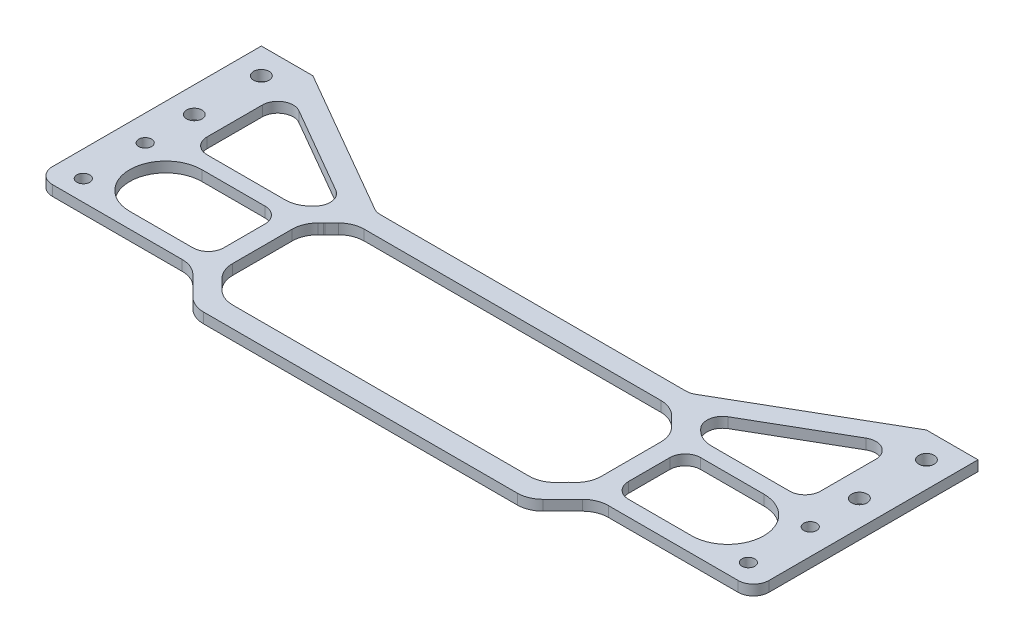
SolidWorks part; units mm, degrees
material "Thornel Mat VMA"
ref_plane "前视基准面" through (0, 0, 0) normal (0, 0, 1) x (1, 0, 0)
ref_plane "上视基准面" through (0, 0, 0) normal (0, 1, 0) x (1, 0, 0)
ref_plane "右视基准面" through (0, 0, 0) normal (1, 0, 0) x (0, 0, -1)
sketch "草图1" plane through (0, 0, 0) normal (0, 1, 0) x (1, 0, 0)
  line L1 (66.5, 10) -> (-66.5, 10)
  line L2 (69.5, 7) -> (69.5, -7)
  line L3 (66.5, -10) -> (-66.5, -10)
  line L4 (-69.5, 7) -> (-69.5, -7)
  line L5 (69.5, 10) -> (-69.5, -10) construction
  line L6 (69.5, -10) -> (-69.5, 10) construction
  arc A0 (69.5, 7) -> (66.5, 10) centre (66.5, 7) ccw
  arc A1 (69.5, -7) -> (66.5, -10) centre (66.5, -7) cw
  arc A2 (-66.5, -10) -> (-69.5, -7) centre (-66.5, -7) cw
  arc A3 (-66.5, 10) -> (-69.5, 7) centre (-66.5, 7) ccw
  point P0 (0, 0)
  dimension "D3" = 3
  dimension "D1" = 20
  dimension "D2" = 139
extrude "凸台-拉伸1" add sketch "草图1" along normal blind 2
sketch "草图2" plane through (0, 2, 0) normal (0, 1, 0) x (1, 0, 0)
  line L1 (64.5, 6) -> (-64.5, 6)
  line L2 (64.5, 6) -> (64.5, -6)
  line L3 (64.5, -6) -> (-64.5, -6)
  line L4 (-64.5, 6) -> (-64.5, -6)
  line L5 (64.5, 6) -> (-64.5, -6) construction
  line L6 (64.5, -6) -> (-64.5, 6) construction
  point P0 (0, 0)
  dimension "D1" = 12
  dimension "D2" = 129
hole_wizard "孔1" positions "草图3" profile "草图4" legacy end condition through all
sketch "草图3" plane through (0, 2, 0) normal (0, 1, 0) x (1, 0, 0)
  point P0 (-64.5, 6)
  point P3 (-64.5, -6)
  point P6 (64.5, -6)
  point P9 (64.5, 6)
sketch "草图4" plane through (-64.5, 2, -6) normal (1, 0, 0) x (0, 0, 1)
  line L0 (0, 0) -> (0, 2)
  line L1 (0, 2) -> (1.25, 2)
  line L2 (1.25, 2) -> (1.25, 0)
  line L3 (1.25, 0) -> (0, 0)
  line L4 (0, 110) -> (0, -10) construction
  dimension "直径" = 2.5
  dimension "深度" = 2
sketch "草图5" plane through (0, 2, 0) normal (0, 1, 0) x (1, 0, 0)
  line L0 (-54.5, 0) -> (54.5, 0) construction
  line L1 (-54.5, 7) -> (54.5, 7)
  line L2 (-54.5, -7) -> (54.5, -7)
  line L3 (66.5, 10) -> (-66.5, 10) construction
  line L4 (-69.5, 7) -> (-69.5, -7) construction
  arc A0 (-54.5, 7) -> (-54.5, -7) centre (-54.5, 0) ccw
  arc A1 (54.5, -7) -> (54.5, 7) centre (54.5, 0) ccw
  point P3 (0, 0)
  dimension "D1" = 3
  dimension "D2" = 15
extrude "切除-拉伸1" cut sketch "草图5" against normal through all
sketch "草图6" plane through (0, 0, 0) normal (0, -1, 0) x (1, 0, 0)
  line L0 (-66.5, 10) -> (66.5, 10) construction
  line L1 (-39.25, -10) -> (39.25, -10)
  line L2 (-39.25, -4) -> (-39.25, 4)
  line L3 (-39.25, 10) -> (39.25, 10)
  line L4 (39.25, -4) -> (39.25, 4)
  line L5 (-39.25, -10) -> (39.25, 10) construction
  line L6 (-39.25, 10) -> (39.25, -10) construction
  line L7 (39.25, -23.75) -> (39.25, 23.75) construction
  line L8 (39.25, 10) -> (46.786, 7)
  line L9 (-54.5, 7) -> (54.5, 7) construction
  line L10 (46.786, 7) -> (42.25, 7)
  line L11 (39.25, -10) -> (46.786, -7)
  line L12 (54.5, -7) -> (-54.5, -7) construction
  line L13 (46.786, -7) -> (42.25, -7)
  line L14 (-39.25, 10) -> (-46.786, 7)
  line L15 (-46.786, 7) -> (-42.25, 7)
  line L16 (-39.25, -10) -> (-46.4944, -7)
  line L17 (-46.4944, -7) -> (-42.25, -7)
  line L18 (-39.25, 23.75) -> (-39.25, -23.75) construction
  arc A0 (39.25, -4) -> (42.25, -7) centre (42.25, -4) ccw
  arc A1 (39.25, 4) -> (42.25, 7) centre (42.25, 4) cw
  arc A2 (-42.25, -7) -> (-39.25, -4) centre (-42.25, -4) ccw
  arc A3 (-39.25, 4) -> (-42.25, 7) centre (-42.25, 4) ccw
  point P0 (0, 0)
  point P26 (39.25, -7)
  point P29 (39.25, 7)
  point P32 (-39.25, -7)
  point P35 (-39.25, 7)
  dimension "D1" = 3
extrude "凸台-拉伸2" add sketch "草图6" against normal blind 2
sketch "草图7" plane through (0, 0, 0) normal (0, -1, 0) x (1, 0, 0)
  line L0 (34.25, 0) -> (-34.25, 0) construction
  line L1 (34.25, -1.5) -> (-34.25, -1.5)
  line L2 (34.25, 1.5) -> (-34.25, 1.5)
  line L3 (39.25, -4) -> (39.25, 4) construction
  line L4 (34.25, 5.5) -> (-34.25, 5.5) construction
  line L5 (34.25, 4) -> (-34.25, 4)
  line L6 (34.25, 7) -> (-34.25, 7)
  line L7 (34.25, -5.5) -> (-34.25, -5.5) construction
  line L8 (34.25, -7) -> (-34.25, -7)
  line L9 (34.25, -4) -> (-34.25, -4)
  arc A0 (34.25, -1.5) -> (34.25, 1.5) centre (34.25, 0) ccw
  arc A1 (-34.25, 1.5) -> (-34.25, -1.5) centre (-34.25, 0) ccw
  arc A2 (34.25, 4) -> (34.25, 7) centre (34.25, 5.5) ccw
  arc A3 (-34.25, 7) -> (-34.25, 4) centre (-34.25, 5.5) ccw
  arc A4 (34.25, -7) -> (34.25, -4) centre (34.25, -5.5) ccw
  arc A5 (-34.25, -4) -> (-34.25, -7) centre (-34.25, -5.5) ccw
  point P3 (0, 0)
  point P14 (0, 5.5)
  point P21 (0, -5.5)
  dimension "D1" = 1.5
  dimension "D2" = 5
  dimension "D4" = 5.5
  dimension "D3" = 2
  dimension "D5" = 2
extrude "切除-拉伸2" cut sketch "草图7" against normal through all both and the other way through all
sketch "草图9" plane through (0, 0, 0) normal (0, -1, 0) x (-1, 0, 0)
  line L0 (47.6578, -10) -> (41.3211, -10)
  line L1 (66.5, -10) -> (-66.5, -10) construction
  line L2 (39.25, -23.75) -> (39.25, 23.75) construction
  line L3 (37.7855, -11.4645) -> (33.9645, -15.2855)
  line L4 (30.4289, -16.75) -> (-30.4289, -16.75)
  line L5 (0, 87.7971) -> (0, -87.7971) construction
  line L6 (39.25, -10) -> (33.5931, -10)
  line L7 (33.5931, -10) -> (32.3076, -11.2855)
  line L8 (28.7721, -12.75) -> (-28.7721, -12.75)
  line L9 (-36.25, -26.75) -> (36.25, -26.75) construction
  line L10 (47.6578, -10) -> (47.6578, -7.8784)
  line L11 (47.6578, -7.8784) -> (24.5865, -7.8784)
  line L12 (24.5865, -7.8784) -> (24.5865, -10)
  line L13 (24.5865, -10) -> (33.5931, -10)
  line L14 (0, -16.75) -> (0, 0) construction
  line L15 (-31.7712, 0) -> (31.7712, 0) construction
  line L16 (24.5865, 10) -> (33.5931, 10)
  line L17 (24.5865, 7.8784) -> (24.5865, 10)
  line L18 (47.6578, 7.8784) -> (24.5865, 7.8784)
  line L19 (47.6578, 10) -> (47.6578, 7.8784)
  line L20 (28.7721, 12.75) -> (-28.7721, 12.75)
  line L21 (33.5931, 10) -> (32.3076, 11.2855)
  line L22 (39.25, 10) -> (33.5931, 10)
  line L23 (30.4289, 16.75) -> (-30.4289, 16.75)
  line L24 (37.7855, 11.4645) -> (33.9645, 15.2855)
  line L25 (47.6578, 10) -> (41.3211, 10)
  line L26 (-47.6578, 10) -> (-41.3211, 10)
  line L27 (-37.7855, 11.4645) -> (-33.9645, 15.2855)
  line L28 (-39.25, 10) -> (-33.5931, 10)
  line L29 (-33.5931, 10) -> (-32.3076, 11.2855)
  line L30 (-47.6578, 10) -> (-47.6578, 7.8784)
  line L31 (-47.6578, 7.8784) -> (-24.5865, 7.8784)
  line L32 (-24.5865, 7.8784) -> (-24.5865, 10)
  line L33 (-24.5865, 10) -> (-33.5931, 10)
  line L34 (-24.5865, -10) -> (-33.5931, -10)
  line L35 (-24.5865, -7.8784) -> (-24.5865, -10)
  line L36 (-47.6578, -7.8784) -> (-24.5865, -7.8784)
  line L37 (-47.6578, -10) -> (-47.6578, -7.8784)
  line L38 (-33.5931, -10) -> (-32.3076, -11.2855)
  line L39 (-39.25, -10) -> (-33.5931, -10)
  line L40 (-37.7855, -11.4645) -> (-33.9645, -15.2855)
  line L41 (-47.6578, -10) -> (-41.3211, -10)
  arc A0 (28.7721, -12.75) -> (32.3076, -11.2855) centre (28.7721, -7.75) ccw
  arc A1 (37.7855, -11.4645) -> (41.3211, -10) centre (41.3211, -15) cw
  arc A2 (30.4289, -16.75) -> (33.9645, -15.2855) centre (30.4289, -11.75) ccw
  arc A3 (30.4289, 16.75) -> (33.9645, 15.2855) centre (30.4289, 11.75) cw
  arc A4 (37.7855, 11.4645) -> (41.3211, 10) centre (41.3211, 15) ccw
  arc A5 (28.7721, 12.75) -> (32.3076, 11.2855) centre (28.7721, 7.75) cw
  arc A6 (-28.7721, 12.75) -> (-32.3076, 11.2855) centre (-28.7721, 7.75) ccw
  arc A7 (-37.7855, 11.4645) -> (-41.3211, 10) centre (-41.3211, 15) cw
  arc A8 (-30.4289, 16.75) -> (-33.9645, 15.2855) centre (-30.4289, 11.75) ccw
  arc A9 (-30.4289, -16.75) -> (-33.9645, -15.2855) centre (-30.4289, -11.75) cw
  arc A10 (-37.7855, -11.4645) -> (-41.3211, -10) centre (-41.3211, -15) ccw
  arc A11 (-28.7721, -12.75) -> (-32.3076, -11.2855) centre (-28.7721, -7.75) cw
  point P65 (0, 16.75)
  point P67 (0, 12.75)
  point P75 (0, -12.75)
  line M31 (66.5, 10) -> (-66.5, 10)
  line M35 (-66.5, -10) -> (66.5, -10)
  dimension "D5" = 5
  dimension "D6" = 5
  dimension "D1" = 4
  dimension "D2" = 45
  dimension "D3" = 4
  dimension "D4" = 10
extrude "凸台-拉伸3" add sketch "草图9" against normal blind 2 contours L8 A11 L38 A10 L40 A9 L4 A2 L3 A1 L7 A0 M35 | L23 A8 L27 A7 L29 A6 L20 A5 L21 A4 L24 A3 M31 region at (0, 0, 14.3452) region at (0, 0, -14.3452)
sketch "草图10" plane through (0, 2, 0) normal (0, 1, 0) x (1, 0, 0)
  line L0 (34.2855, -9.3076) -> (34.098, -9.4951)
  line L2 (-35.75, -5.7721) -> (-35.75, 5.7721)
  line L4 (35.75, -5.7721) -> (35.75, 5.7721)
  line L5 (-35.75, -7.8431) -> (35.75, 7.8431) construction
  line L6 (-35.75, 7.8431) -> (35.75, -7.8431) construction
  line L7 (33.5931, -10) -> (32.3076, -11.2855) construction
  line L8 (30.5884, -10.9595) -> (-30.2214, -11.2747)
  line L9 (-33.7828, -9.8103) -> (-34.2855, -9.3076)
  line L10 (34.2855, 9.3076) -> (33.7721, 9.8211)
  line L11 (30.2365, 11.2855) -> (-30.2365, 11.2855)
  line L12 (-33.7721, 9.8211) -> (-34.2855, 9.3076)
  arc A0 (34.25, 4) -> (34.25, 7) centre (34.25, 5.5) ccw construction
  arc A1 (-35.75, -5.7721) -> (-34.2855, -9.3076) centre (-30.75, -5.7721) ccw
  arc A2 (-33.7828, -9.8103) -> (-30.2214, -11.2747) centre (-30.2473, -6.2748) ccw
  arc A3 (-35.75, 5.7721) -> (-34.2855, 9.3076) centre (-30.75, 5.7721) cw
  arc A4 (-33.7721, 9.8211) -> (-30.2365, 11.2855) centre (-30.2365, 6.2855) cw
  arc A5 (30.2365, 11.2855) -> (33.7721, 9.8211) centre (30.2365, 6.2855) cw
  arc A6 (34.2855, 9.3076) -> (35.75, 5.7721) centre (30.75, 5.7721) cw
  arc A7 (35.75, -5.7721) -> (34.2855, -9.3076) centre (30.75, -5.7721) cw
  arc A8 (30.5884, -10.9595) -> (34.098, -9.4951) centre (30.5625, -5.9596) ccw
  point P0 (0, 0)
  point P23 (-32.3076, -11.2855)
  point P29 (-32.3076, 11.2855)
  point P32 (32.3076, 11.2855)
  point P41 (32.6443, -10.9489)
  dimension "D1" = 5
extrude "切除-拉伸3" cut sketch "草图10" against normal through all both and the other way through all
sketch "草图11" plane through (0, 0, 0) normal (0, -1, 0) x (1, 0, 0)
  line L0 (-69.5, -7) -> (-69.5, -33.5342)
  line L1 (-69.5, -10) -> (-69.5, -220) construction
  line L2 (-69.5, -33.5342) -> (-59.5, -33.5342)
  line L3 (-59.5, -10) -> (-59.5, -220) construction
  line L4 (-30.4289, -16.75) -> (30.4289, -16.75) construction
  line L5 (-59.5, -33.5342) -> (-31.1251, -17.1519)
  line L6 (0, -12.75) -> (0, -36.5409) construction
  line L7 (-38.056, -16.5347) -> (-55, -26.3173)
  line L8 (-59.5, -23.7192) -> (-59.5, -13)
  line L9 (-41.3211, -10) -> (-66.5, -10) construction
  line L10 (-56.5, -10) -> (-53.1843, -10)
  line L11 (-53.1843, -10) -> (-53.1843, -7.988)
  line L12 (-53.1843, -7.988) -> (-66.362, -7.988)
  line L13 (-66.362, -7.988) -> (-69.5, -7)
  line L14 (-39.9409, -9.3091) -> (-37.4347, -11.8153)
  line L15 (-37.7855, -11.4645) -> (-33.9645, -15.2855) construction
  line L16 (-39.9409, -9.3091) -> (-32.2298, -13.6308)
  line L17 (-32.2298, -13.6308) -> (-21.7891, -16.75)
  line L18 (-21.7891, -16.75) -> (-29.6251, -16.75)
  line L19 (-28.7721, -12.75) -> (28.7721, -12.75) construction
  line L20 (0, -87.7971) -> (0, 87.7971) construction
  line L21 (21.7891, -16.75) -> (29.6251, -16.75)
  line L22 (32.2298, -13.6308) -> (21.7891, -16.75)
  line L23 (39.9409, -9.3091) -> (32.2298, -13.6308)
  line L24 (39.9409, -9.3091) -> (37.4347, -11.8153)
  line L25 (66.362, -7.988) -> (69.5, -7)
  line L26 (53.1843, -7.988) -> (66.362, -7.988)
  line L27 (53.1843, -10) -> (53.1843, -7.988)
  line L28 (56.5, -10) -> (53.1843, -10)
  line L29 (59.5, -23.7192) -> (59.5, -13)
  line L30 (38.056, -16.5347) -> (55, -26.3173)
  line L31 (59.5, -33.5342) -> (31.1251, -17.1519)
  line L32 (69.5, -33.5342) -> (59.5, -33.5342)
  line L33 (69.5, -7) -> (69.5, -33.5342)
  arc A0 (-38.056, -16.5347) -> (-37.4347, -11.8153) centre (-39.556, -13.9366) ccw
  arc A1 (-55, -26.3173) -> (-59.5, -23.7192) centre (-56.5, -23.7192) cw
  arc A2 (-59.5, -13) -> (-56.5, -10) centre (-56.5, -13) cw
  arc A3 (-29.6251, -16.75) -> (-31.1251, -17.1519) centre (-29.6251, -19.75) ccw
  arc A4 (29.6251, -16.75) -> (31.1251, -17.1519) centre (29.6251, -19.75) cw
  arc A5 (59.5, -13) -> (56.5, -10) centre (56.5, -13) ccw
  arc A6 (55, -26.3173) -> (59.5, -23.7192) centre (56.5, -23.7192) ccw
  arc A7 (38.056, -16.5347) -> (37.4347, -11.8153) centre (39.556, -13.9366) cw
  point P25 (-30.4289, -16.75)
  point P28 (-34.6701, -14.5799)
  point P31 (-59.5, -28.9154)
  point P34 (-59.5, -10)
  point P64 (59.5, -10)
  point P65 (59.5, -28.9154)
  point P66 (34.6701, -14.5799)
  point P67 (30.4289, -16.75)
  dimension "D1" = 3
  dimension "D3" = 3
  dimension "D2" = 150
  dimension "D4" = 4
extrude "凸台-拉伸4" add sketch "草图11" against normal blind 2
hole_wizard "孔2" positions "草图12" profile "草图13" legacy end condition through all
sketch "草图12" plane through (0, 0, 0) normal (0, -1, 0) x (-1, 0, 0)
  point P0 (64.5, 15.5342)
  point P3 (64.5, 28.5342)
  point P6 (-64.5, 15.5342)
  point P9 (-64.5, 28.5342)
sketch "草图13" plane through (-64.5, 0, -15.5342) normal (1, 0, 0) x (0, 0, -1)
  line L0 (0, 0) -> (0, 2)
  line L1 (0, 2) -> (1.5, 2)
  line L2 (1.5, 2) -> (1.5, 0)
  line L3 (1.5, 0) -> (0, 0)
  line L4 (0, 110) -> (0, -10) construction
  dimension "直径" = 3
  dimension "深度" = 2
